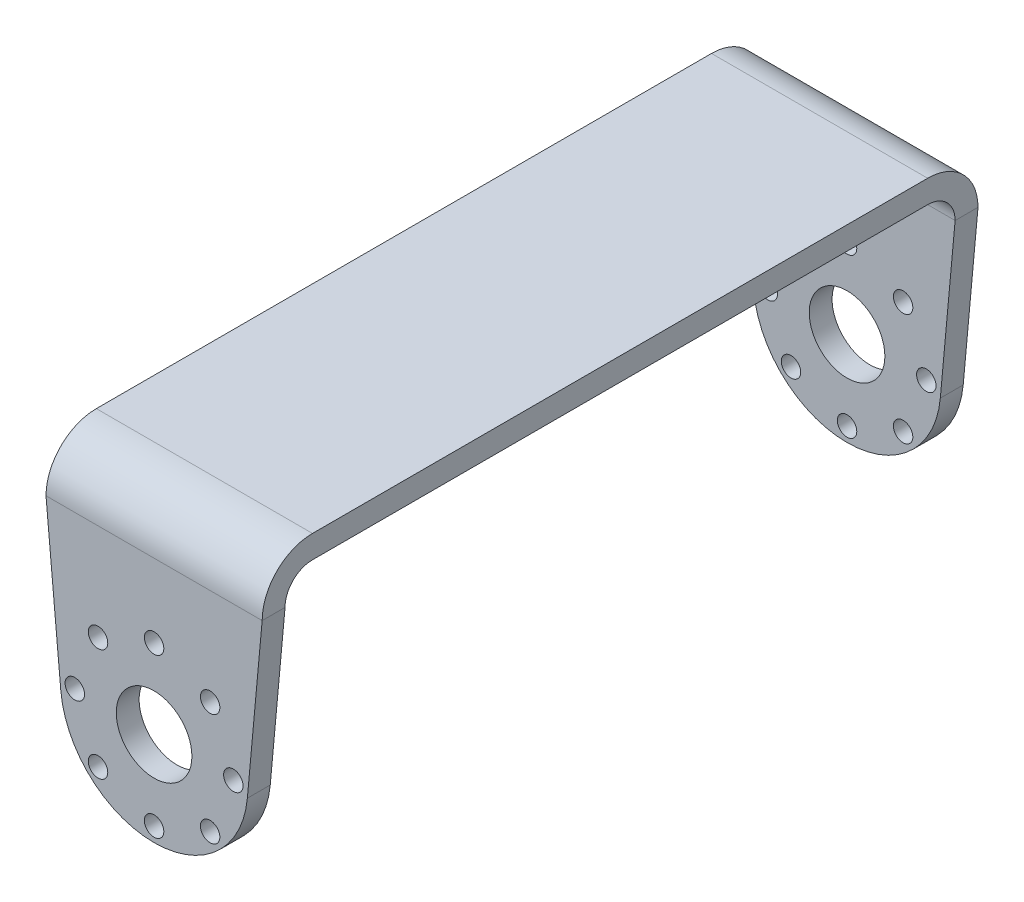
SolidWorks part; units mm, degrees
note: The reader was unsure of these and kept them because the rebuilt part matched: flange length of "Edge-Flange1".
ref_plane "Front Plane" through (0, 0, 0) normal (0, 0, 1) x (1, 0, 0)
ref_plane "Top Plane" through (0, 0, 0) normal (0, 1, 0) x (1, 0, 0)
ref_plane "Right Plane" through (0, 0, 0) normal (1, 0, 0) x (0, 0, -1)
sketch "Sketch1" plane through (0, 0, 0) normal (0, 1, 0) x (1, 0, 0)
  line L1 (-15, -46.5) -> (15, -46.5)
  line L2 (-15, -46.5) -> (-15, 46.5)
  line L3 (-15, 46.5) -> (15, 46.5)
  line L4 (15, -46.5) -> (15, 46.5)
  line L5 (-15, -46.5) -> (15, 46.5) construction
  line L6 (-15, 46.5) -> (15, -46.5) construction
  point P0 (0, 0)
  dimension "D1" = 30
  dimension "D2" = 93
base flange "Base-Flange1" sketch "Sketch1" thickness 3.175 reverse thickness direction yes parameters "D1"=3.81
edge flange "Edge-Flange1" sketch "Sketch10" flange profiles "Sketch10", "Sketch11" flange angle 90 flange length 38 flange position material outside bend radius 3.81 thickness 3.175 relief rectangular parameters "D6"=10, "D8"=1
sketch "Sketch10" plane through (0, 0, 46.5) normal (0, 0, 1) x (-1, 0, 0)
  line L2 (-15, 0) -> (-15, 38)
  line L3 (-15, 38) -> (15, 38)
  line L4 (15, 38) -> (15, 0)
  line L7 (15, 0) -> (-15, 0) construction
  line L8 (15, 0) -> (-15, 0)
sketch "Sketch11" plane through (0, 0, -46.5) normal (0, 0, -1) x (1, 0, 0)
  line L0 (15, 0) -> (-15, 0) construction
  line L1 (15, 0) -> (-15, 0)
  line L2 (-15, 0) -> (-15, 38)
  line L3 (-15, 38) -> (15, 38)
  line L4 (15, 38) -> (15, 0)
bend "EdgeBend1" bend radius 3.81 bend angle 90 parameters "D5"=1
bend "EdgeBend2" bend radius 3.81 bend angle 90 parameters "D5"=2
sketch "Sketch12" plane through (0, 0, 0) normal (0, 0, 1) x (1, 0, 0)
  line L0 (-15, 0) -> (15, 0)
  line L1 (-15, 0) -> (15, 0) construction
  line L2 (0, 0) -> (0, -25) construction
  line L3 (0, -25) -> (0, -36) construction
  line L4 (12.9456, -26.1885) -> (15, -3.81)
  line L5 (-12.9456, -26.1885) -> (-15, -3.81)
  line L7 (15, -3.81) -> (15, 3.175)
  line L8 (15, 3.175) -> (-15, 3.175)
  line L9 (-15, 3.175) -> (-15, -3.81)
  arc A0 (-12.9456, -26.1885) -> (12.9456, -26.1885) centre (0, -25) ccw
  circle A3 centre (0, -36) radius 1.35
  circle A4 centre (-7.7782, -32.7782) radius 1.35
  circle A5 centre (-11, -25) radius 1.35
  circle A6 centre (-7.7782, -17.2218) radius 1.35
  circle A7 centre (0, -14) radius 1.35
  circle A8 centre (7.7782, -17.2218) radius 1.35
  circle A9 centre (11, -25) radius 1.35
  circle A10 centre (7.7782, -32.7782) radius 1.35
  circle A11 centre (0, -25) radius 5.25
  point P29 (0, -25)
  dimension "D2" = 26
  dimension "D4" = 2.7
  dimension "D6" = 10.5
  dimension "D1" = 25
  dimension "D3" = 11
  dimension "D5" = 8
extrude "Cut-Extrude1" cut sketch "Sketch12" against normal through all and the other way through all flip side to cut
sketch "Bend-Lines1" [suppressed] plane through (0, 0, 0) normal (0, 1, 0) x (1, 0, 0)
sketch "Bounding-Box1" [suppressed] plane through (0, 0, 0) normal (0, 1, 0) x (1, 0, 0)
sheet metal parameters "Sheet-Metal1" thickness 3.175 parameters "D1"=3.81
flat pattern "Flat-Pattern1" [suppressed]
sketch "Bend-Lines2" plane through (0, 0, 0) normal (0, 1, 0) x (1, 0, 0)
sketch3d "Bounding-Box2" [suppressed]
  line L0 (15, -46.5, 0) -> (15, 46.5, 0) construction
  line L1 (-15, -46.5, 0) -> (-15, 46.5, 0) construction
  line L2 (15, -46.5, 0) -> (-15, -46.5, 0) construction
  line L3 (15, 46.5, 0) -> (-15, 46.5, 0) construction
sheet metal parameters "Sheet-Metal2" thickness 3.175 parameters "D1"=3.81
flat pattern "Flat-Pattern1"
sketch "Bend-Lines2" plane through (0, 0, 0) normal (0, -1, 0) x (-1, 0, 0)
  line L0 (15, 46.6299) -> (-15, 46.6299) construction
  line L1 (-15, -46.6299) -> (15, -46.6299) construction
  line L2 (15, 46.6299) -> (-15, 46.6299) construction
  line L3 (-15, -46.6299) -> (15, -46.6299) construction
sketch3d "Bounding-Box2" [suppressed]
  line L0 (15, -84.7599, 0) -> (15, 84.7599, 0) construction
  line L1 (-15, -84.7599, 0) -> (-15, 84.7599, 0) construction
  line L2 (15, -84.7599, 0) -> (-15, -84.7599, 0) construction
  line L3 (15, 84.7599, 0) -> (-15, 84.7599, 0) construction
bend of the flat pattern "Flatten-<EdgeBend1>1"
bend of the flat pattern "Flatten-<EdgeBend2>1"
sheet metal parameters "Sheet-Metal3" thickness 3.175 parameters "D1"=3.81
flat pattern "Flat-Pattern1"
sketch "Bend-Lines2" plane through (0, 0, 0) normal (0, -1, 0) x (-1, 0, 0)
  line L0 (15, 46.6299) -> (-15, 46.6299) construction
  line L1 (-15, -46.6299) -> (15, -46.6299) construction
  line L2 (15, 46.6299) -> (-15, 46.6299) construction
  line L3 (-15, -46.6299) -> (15, -46.6299) construction
sketch3d "Bounding-Box2" [suppressed]
  line L0 (15, -84.7599, 0) -> (15, 84.7599, 0) construction
  line L1 (-15, -84.7599, 0) -> (-15, 84.7599, 0) construction
  line L2 (15, -84.7599, 0) -> (-15, -84.7599, 0) construction
  line L3 (15, 84.7599, 0) -> (-15, 84.7599, 0) construction
bend of the flat pattern "Flatten-<EdgeBend1>1"
bend of the flat pattern "Flatten-<EdgeBend2>1"
